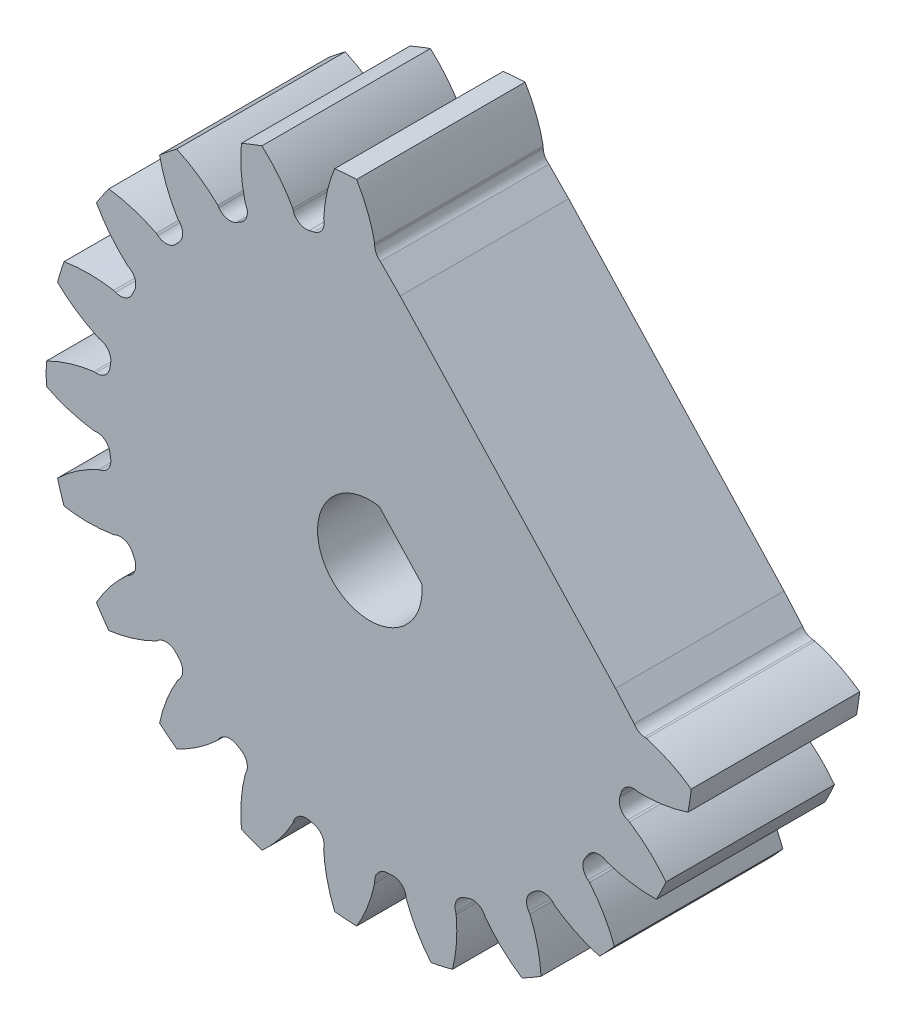
SolidWorks part; units mm, degrees
ref_plane "Front" through (0, 0, 0) normal (0, 0, 1) x (1, 0, 0)
ref_plane "Top" through (0, 0, 0) normal (0, 1, 0) x (1, 0, 0)
ref_plane "Right" through (0, 0, 0) normal (1, 0, 0) x (0, 0, -1)
sketch "Sketch1" plane through (0, 0, 0) normal (0, 0, 1) x (1, 0, 0)
  line L0 (-266.7, 0) -> (266.7, 0) construction
  circle A0 centre (0, 0) radius 24.384
  circle A1 centre (0, 0) radius 22.225 construction
  circle A3 centre (0, 0) radius 19.776 construction
  dimension "D1" = 2.449
  dimension "D2" = 4.608
  dimension "D3" = 2.159
extrude "Boss-Extrude1" add sketch "Sketch1" against normal blind 25.4
sketch "Sketch2" plane through (0, 0, 0) normal (1, 0, 0) x (0, 0, -1)
  line L0 (25.4, 0) -> (41.148, 0)
  line L1 (25.4, 0) -> (25.4, 17.78)
  line L2 (25.4, 17.78) -> (41.148, 17.78)
  line L3 (41.148, 17.78) -> (41.148, 0)
  point P5 (41.148, -17.78)
  point P6 (0, -24.384)
  point P7 (25.4, -24.384)
  point P9 (0, 24.384)
revolve "Revolve1" add sketch "Sketch2" angle 360 mid plane about L0
fillet "Fillet2" radius 0.4877 3 edges at (24.384, 0, -25.4) (24.384, 0, 0) (17.78, 0, -25.4)
sketch "Sketch3" plane through (0, 0, 0) normal (0, 0, 1) x (1, 0, 0)
  line L0 (0, 0) -> (0, 24.384) construction
  line L1 (-7.143, 19.6252) -> (0, 22.225)
  line L2 (-9.5921, 22.225) -> (9.5921, 22.225) construction
  line L3 (-9.0136, 18.9443) -> (9.0136, 25.5057) construction
  line L4 (-7.143, 19.6252) -> (0, 0) construction
  line L5 (-17.4143, 11.5287) -> (0, 0) construction
  line L6 (-17.4143, 11.5287) -> (-5.875, 28.959) construction
  line L7 (-4.9618, 20.2867) -> (0, 0) construction
  line L8 (-4.9618, 20.2867) -> (0.2068, 21.5509) construction
  arc A0 (-7.143, 19.6252) -> (-17.4143, 11.5287) centre (0, 0) ccw
  circle A1 centre (0, 0) radius 22.225 construction
  circle A2 centre (0, 0) radius 20.8847 construction
  arc A3 (-7.143, 19.6252) -> (-4.9618, 20.2867) centre (0, 0) cw
  circle A4 centre (0, 0) radius 24.384 construction
  point P6 (0, 22.225)
  dimension "D1" = 7.6014
  dimension "D3" = 20.9038
  dimension "D5" = 5.321
  dimension "D2" = 13.3024
  dimension "D4" = 2.2804
sketch "Sketch4" plane through (0, 0, 0) normal (0, 0, 1) x (1, 0, 0)
  line L0 (0, 0) -> (1.6562, 22.1009) construction
  line L1 (0.3689, 20.8814) -> (0.3689, 19.7726)
  line L2 (0, 22.225) -> (3.3125, 21.9768) construction
  line L3 (2.7474, 20.7032) -> (2.5821, 19.6067)
  line L4 (0.3689, 19.7726) -> (0, 0) construction
  line L5 (0, 0) -> (0, 24.384) construction
  line L6 (-17.4143, 11.5287) -> (-5.875, 28.959) construction
  line L7 (-17.4143, 11.5287) -> (-5.875, 28.959) construction
  arc A0 (2.5821, 19.6067) -> (0.3689, 19.7726) centre (0, 0) ccw
  arc A1 (0, 22.225) -> (3.3125, 21.9768) centre (0, 0) cw construction
  circle A2 centre (0, 0) radius 22.225 construction
  circle A3 centre (0, 0) radius 20.8847 construction
  circle A4 centre (0, 0) radius 19.776 construction
  arc A5 (10.1255, 27.7599) -> (-5.875, 28.959) centre (0, 0) ccw
  spline S0 degree 2 poles (-5.875, 28.959) (-0.7026, 25.9425) (0.3689, 20.8814) knots 0 0 0 1 1 1
  spline S1 degree 2 poles (10.1255, 27.7599) (4.5613, 25.548) (2.7474, 20.7032) knots 0 0 0 1 1 1
  dimension "D1" = 3.3249
extrude "Cut-Extrude1" cut sketch "Sketch4" against normal through all
fillet "Fillet1" radius 0.9975 2 edges at (2.5821, 19.6067, -12.7) (0.3689, 19.7726, -12.7)
pattern_circular "CirPattern1" count 21 over 360 about axis through (0, 0, -25.4) along (0, 0, 1) of "Cut-Extrude1", "Fillet1"
sketch "Sketch5" plane through (0, 0, 0) normal (0, 0, 1) x (1, 0, 0)
  circle A0 centre (0, 0) radius 3.937
  circle A1 centre (0, 0) radius 3.937 construction
  dimension "Bore Min" = 7.874
  dimension "Bore Max" = 7.874
extrude "Cut-Extrude2" cut sketch "Sketch5" against normal through all
chamfer "Chamfer1" distance 0.889 angle 45 3 edges at (17.78, 0, -41.148) (3.937, 0, 0) (3.937, 0, -41.148)
sketch "Pitch Dia" plane through (0, 0, 0) normal (0, 0, 1) x (1, 0, 0)
  circle A0 centre (0, 0) radius 22.225 construction
  circle A1 centre (0, 0) radius 22.225 construction
sketch "Sketch6" plane through (0, 0, -41.148) normal (0, 0, -1) x (-1, 0, 0)
  circle A0 centre (0, 0) radius 34.0137
extrude "Cut-Extrude3" cut sketch "Sketch6" against normal blind 21.59
sketch "Sketch7" plane through (0, 0, 0) normal (0, 0, 1) x (1, 0, 0)
  circle A0 centre (0, 0) radius 30.7492
extrude "Cut-Extrude4" cut sketch "Sketch7" against normal blind 6.858
sketch "Sketch8" plane through (0, 0, 0) normal (0, 1, 0) x (1, 0, 0)
  line L1 (19.776, 6.858) -> (27.396, 6.858)
  line L2 (19.776, 6.858) -> (19.776, 19.558)
  line L3 (19.776, 19.558) -> (27.396, 19.558)
  line L4 (27.396, 6.858) -> (27.396, 19.558)
  dimension "D1" = 12.7
  dimension "D2" = 7.62
revolve "Cut-Revolve1" cut sketch "Sketch8" angle 85.714 about axis through (0, 0, -25.4) along (0, 0, 1)
sketch "Sketch10" plane through (0, 0, -6.858) normal (0, 0, 1) x (1, 0, 0)
  line L0 (-0.9956, 24.3637) -> (24.2211, -2.8135)
  line L1 (-0.9956, 24.3637) -> (1.8885, 27.0397)
  line L2 (1.8885, 27.0397) -> (27.1052, -0.1375)
  line L3 (27.1052, -0.1375) -> (24.2211, -2.8135)
  arc A0 (19.7752, -0.1775) -> (1.3008, 19.7332) centre (0, 0) ccw construction
  point P9 (0, 0)
extrude "Cut-Extrude5" cut sketch "Sketch10" against normal through all
sketch "Sketch11" plane through (0, 0, -6.858) normal (0, 0, 1) x (1, 0, 0)
  line L0 (0.7177, 3.871) -> (3.9138, 0.4264)
  line L1 (3.561, 19.4528) -> (19.6645, 2.0974) construction
  line L2 (0.7177, 3.871) -> (2.3158, 5.3538)
  line L3 (2.3158, 5.3538) -> (5.5119, 1.9092)
  line L4 (5.5119, 1.9092) -> (3.9138, 0.4264)
  circle A0 centre (0, 0) radius 3.937 construction
  dimension "D1" = 4.699
extrude "Boss-Extrude2" add sketch "Sketch11" against normal blind 12.7
sketch "Sketch17" plane through (0, 0, -6.858) normal (0, 0, 1) x (1, 0, 0)
  line L0 (0, 0) -> (24.1117, -3.6343) construction
  line L1 (0, 0) -> (22.225, -3.3499)
  line L2 (0, 0) -> (-3.9786, -26.3965) construction
  arc A0 (23.9744, -4.4508) -> (24.2211, -2.8135) centre (0, 0) ccw construction
  dimension "D1" = 22.225
sketch "Sketch20" plane through (0, 0, -6.858) normal (0, 0, 1) x (1, 0, 0)
  line L0 (0, 0) -> (22.225, 0.5543)
  line L1 (0, 0) -> (22.225, -3.3499) construction
  line L2 (0, 0) -> (0.4193, -16.8127)
  dimension "D1" = 10
  dimension "D2" = 22.225
sketch "Sketch21" plane through (0, 0, -6.858) normal (0, 0, 1) x (1, 0, 0)
  circle A0 centre (0, 0) radius 24.384
  dimension "D1" = 48.768
sketch "Sketch23" plane through (11.6128, 10.7751, 0) normal (0.7331, 0.6802, 0) x (0, 0, -1)
  line L1 (6.2871, 14.3034) -> (20.3415, 14.3034)
  line L2 (6.2871, 14.3034) -> (6.2871, -14.2793)
  line L3 (6.2871, -14.2793) -> (20.3415, -14.2793)
  line L4 (20.3415, 14.3034) -> (20.3415, -14.2793)
extrude "Cut-Extrude6" cut sketch "Sketch23" against normal blind 1.651
chamfer "Chamfer2" distance 2.54 angle 10 2 edges at (19.8277, -0.5059, -13.208) (0.9773, 19.8101, -13.208) first distance on face at (10.4025, 9.6521, -13.208)
equation "\"D1@Boss-Extrude1\" = \"Face Wd@Sketch2\""
equation "\"D2@Sketch3\" = \"D1@Sketch3\"*1.75"
equation "\"D3@Sketch3\" = \"D1@Sketch3\"+\"D2@Sketch3\""
equation "\"D4@Sketch3\" = \"D1@Sketch3\"*.3"
equation "\"D5@Sketch3\" = \"D1@Sketch3\"-\"D4@Sketch3\""
equation "\"D1@Sketch4\" = 1.5708/(\"Number of Teeth@Sketch1\"/\"Ptich Dia@Sketch1\")"
equation "\"D1@Chamfer1\" = \"B Hub Dia@Sketch2\"*.025"
equation "\"D1@CirPattern1\" = \"Number of Teeth@Sketch1\""
equation "\"D1@Fillet1\" = \"D1@Sketch4\"*.3"
equation "\"D1@Fillet2\" = \"OD@Sketch1\"*.01"
equation "\"D1@Sketch1\" = 1.157/(\"Number of Teeth@Sketch1\"/\"Ptich Dia@Sketch1\")"
